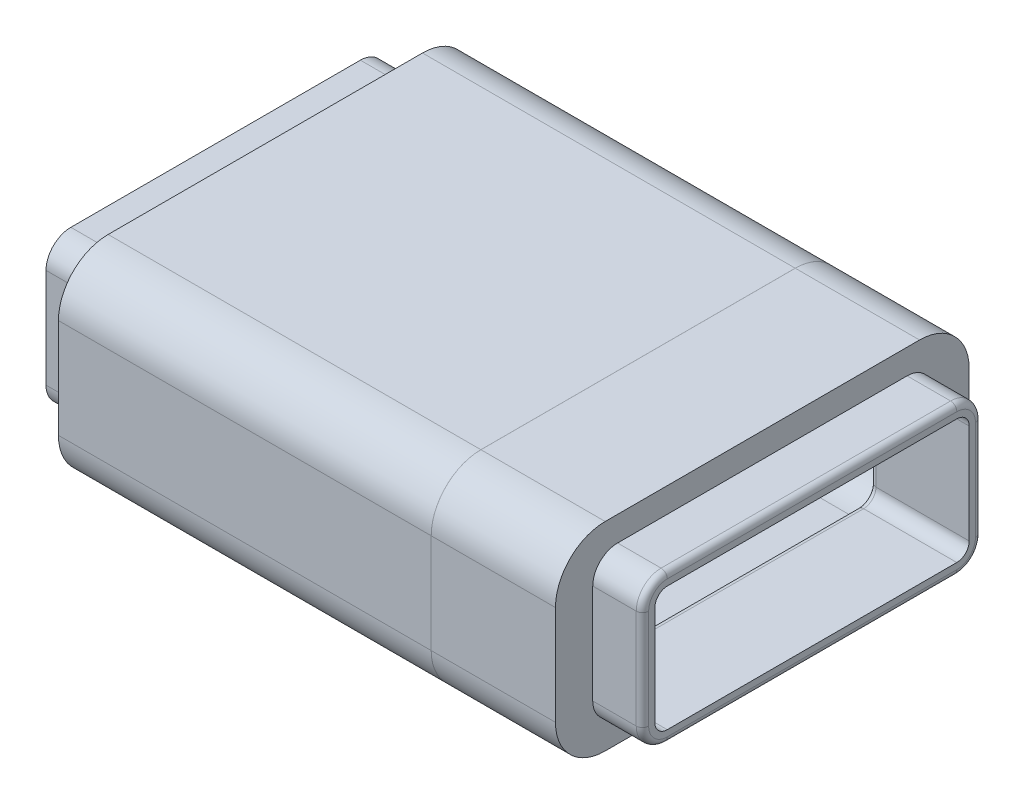
SolidWorks part; units mm, degrees
note: '?' marks a value the reader was unsure of.
ref_plane "Front" through (0, 0, 0) normal (0, 0, 1) x (1, 0, 0)
ref_plane "Top" through (0, 0, 0) normal (0, 1, 0) x (1, 0, 0)
ref_plane "Right" through (0, 0, 0) normal (1, 0, 0) x (0, 0, -1)
ref_plane "Plane4 polowki" through (0, 0, 0) normal (0, 0, 1) x (1, 0, 0)
sketch "Sketch2path" plane through (0, 0, 0) normal (0, 0, 1) x (1, 0, 0)
  line L0 (30.0026, 0) -> (40.0026, -0.0017)
  line L1 (0, 0) -> (30, 0)
  arc A1 (30, 0) -> (30.0026, 0) centre (30, -15) cw
  point P5 (30.0013, 0)
  dimension "D1" = 30
  dimension "D2" = 0.01
  dimension "D4" = 15
  dimension "D3" = 10
sketch "Sketch3" plane through (0, 0, 0) normal (1, 0, 0) x (0, 0, -1)
  line L0 (-16.65, -4) -> (-16.65, 4)
  line L1 (-12.65, 8) -> (12.65, 8)
  line L2 (16.65, 4) -> (16.65, -4)
  line L3 (12.65, -8) -> (-12.65, -8)
  line L4 (-15.65, -4) -> (-15.65, 4)
  line L5 (12.65, -7) -> (-12.65, -7)
  line L6 (0, 91.8161) -> (0, -91.8161) construction
  line L12 (15.65, 4) -> (15.65, -4)
  line L13 (-12.65, 7) -> (12.65, 7)
  arc A0 (-12.65, 8) -> (-16.65, 4) centre (-12.65, 4) ccw
  arc A1 (16.65, 4) -> (12.65, 8) centre (12.65, 4) ccw
  arc A2 (12.65, -8) -> (16.65, -4) centre (12.65, -4) ccw
  arc A3 (-16.65, -4) -> (-12.65, -8) centre (-12.65, -4) ccw
  arc A4 (-12.65, 7) -> (-15.65, 4) centre (-12.65, 4) ccw
  arc A5 (-15.65, -4) -> (-12.65, -7) centre (-12.65, -4) ccw
  arc A10 (12.65, -7) -> (15.65, -4) centre (12.65, -4) ccw
  arc A11 (15.65, 4) -> (12.65, 7) centre (12.65, 4) ccw
  dimension "D1" = 4
  dimension "D2" = 3
  dimension "D3" = 15.65
  dimension "D4" = 15.65
  dimension "D5" = 7
  dimension "D6" = 7
sweep "Sweep1" add profiles "Sketch3" path "Sketch2path"
ref_point "Point1S1"
ref_point "Point2S3"
ref_axis "os podluzna S1" through (0, 0, 0) along (-1, 0, 0)?
ref_axis "os podluzna S3" through (40.0026, -0.0017, 0) along (1, -0.0002, 0)?
sketch "Sketch4" plane through (40.0026, -0.007, 0) normal (1, -0.0002, 0) x (0, 0, -1)
  line L4 (0, 6.0052) -> (-11.65, 6.0052)
  line L5 (-13.65, 0) -> (-12.65, 0)
  line L6 (0, 5.0052) -> (0, 6.0052)
  line L8 (-12.65, -4.9948) -> (12.65, -4.9948)
  line L9 (13.65, -3.9948) -> (13.65, 4.0052)
  line L10 (12.65, 5.0052) -> (-12.65, 5.0052)
  line L11 (-13.65, 4.0052) -> (-13.65, -3.9948)
  line L14 (0, 5.0052) -> (-11.65, 5.0052)
  line L15 (-13.65, 4.0052) -> (-13.65, 0)
  line L16 (0, 0) -> (-20.2541, 0) construction
  line L17 (0, 0) -> (0, 12.5099) construction
  line L19 (-14.65, 4.0052) -> (-14.65, -3.9948) construction
  line L20 (-13.65, 4.0052) -> (-13.65, -3.9948) construction
  line L21 (-12.65, -4.9948) -> (12.65, -4.9948) construction
  line L22 (-12.65, -5.9948) -> (12.65, -5.9948) construction
  line L23 (14.65, -3.9948) -> (14.65, 4.0052) construction
  line L24 (13.65, -3.9948) -> (13.65, 4.0052) construction
  line L25 (12.65, 5.0052) -> (-12.65, 5.0052) construction
  line L26 (12.65, 6.0052) -> (-12.65, 6.0052) construction
  line L27 (-12.65, 4.0052) -> (-12.65, 0)
  line L28 (-13.65, 4.0052) -> (-13.65, 0)
  arc A5 (-11.65, 6.0052) -> (-13.65, 4.0052) centre (-11.65, 4.0052) ccw
  arc A6 (-11.65, 5.0052) -> (-12.65, 4.0052) centre (-11.65, 4.0052) ccw
  arc A8 (-13.65, -3.9948) -> (-12.65, -4.9948) centre (-12.65, -3.9948) ccw
  arc A9 (12.65, -4.9948) -> (13.65, -3.9948) centre (12.65, -3.9948) ccw
  arc A10 (13.65, 4.0052) -> (12.65, 5.0052) centre (12.65, 4.0052) ccw
  arc A11 (-12.65, 5.0052) -> (-13.65, 4.0052) centre (-12.65, 4.0052) ccw
  arc A16 (-14.65, -3.9948) -> (-12.65, -5.9948) centre (-12.65, -3.9948) ccw construction
  arc A17 (-13.65, -3.9948) -> (-12.65, -4.9948) centre (-12.65, -3.9948) ccw construction
  arc A18 (12.65, -4.9948) -> (13.65, -3.9948) centre (12.65, -3.9948) ccw construction
  arc A19 (12.65, -5.9948) -> (14.65, -3.9948) centre (12.65, -3.9948) ccw construction
  arc A20 (14.65, 4.0052) -> (12.65, 6.0052) centre (12.65, 4.0052) ccw construction
  arc A21 (13.65, 4.0052) -> (12.65, 5.0052) centre (12.65, 4.0052) ccw construction
  arc A22 (-12.65, 5.0052) -> (-13.65, 4.0052) centre (-12.65, 4.0052) ccw construction
  arc A23 (-12.65, 6.0052) -> (-14.65, 4.0052) centre (-12.65, 4.0052) ccw construction
  dimension "D1" = 3
  dimension "D2" = 1
extrude "Boss-Extrude1" add sketch "Sketch4" along normal mid plane 8 separate body contours A6 L14 L6 L4 A5 L15 L5 L27
mirror "Mirror1" about plane through (0, 0, 0) normal (0, 0, 1) of bodies 203
mirror "Mirror2" about plane through (44.0026, -0.0077, 0) normal (0.0002, 1, 0) of bodies 204
sketch "Sketch5" plane through (40.0026, -0.007, 0) normal (1, -0.0002, 0) x (0, 0, -1)
  line L0 (-15.65, 4.0052) -> (-15.65, -3.9948) construction
  line L1 (12.65, 7.0052) -> (-12.65, 7.0052) construction
  line L2 (15.65, -3.9948) -> (15.65, 4.0052) construction
  line L3 (-12.65, -6.9948) -> (12.65, -6.9948) construction
  line L4 (-15.65, 4.0052) -> (-15.65, -3.9948)
  line L5 (12.65, 7.0052) -> (-12.65, 7.0052)
  line L6 (15.65, -3.9948) -> (15.65, 4.0052)
  line L7 (-12.65, -6.9948) -> (12.65, -6.9948)
  line L8 (-13.65, 4.0052) -> (-13.65, -4.0052) construction
  line L9 (11.65, 6.0052) -> (-11.65, 6.0052) construction
  line L10 (13.65, 4.0052) -> (13.65, -4.0052) construction
  line L11 (11.65, -6.0052) -> (-11.65, -6.0052) construction
  line L12 (-13.65, 4.0052) -> (-13.65, -4.0052)
  line L13 (11.65, 6.0052) -> (-11.65, 6.0052)
  line L14 (13.65, 4.0052) -> (13.65, -4.0052)
  line L15 (11.65, -6.0052) -> (-11.65, -6.0052)
  arc A0 (-12.65, 7.0052) -> (-15.65, 4.0052) centre (-12.65, 4.0052) ccw construction
  arc A1 (15.65, 4.0052) -> (12.65, 7.0052) centre (12.65, 4.0052) ccw construction
  arc A2 (12.65, -6.9948) -> (15.65, -3.9948) centre (12.65, -3.9948) ccw construction
  arc A3 (-15.65, -3.9948) -> (-12.65, -6.9948) centre (-12.65, -3.9948) ccw construction
  arc A4 (-12.65, 7.0052) -> (-15.65, 4.0052) centre (-12.65, 4.0052) ccw
  arc A5 (15.65, 4.0052) -> (12.65, 7.0052) centre (12.65, 4.0052) ccw
  arc A6 (12.65, -6.9948) -> (15.65, -3.9948) centre (12.65, -3.9948) ccw
  arc A7 (-15.65, -3.9948) -> (-12.65, -6.9948) centre (-12.65, -3.9948) ccw
  arc A8 (-11.65, 6.0052) -> (-13.65, 4.0052) centre (-11.65, 4.0052) ccw construction
  arc A9 (13.65, 4.0052) -> (11.65, 6.0052) centre (11.65, 4.0052) ccw construction
  arc A10 (11.65, -6.0052) -> (13.65, -4.0052) centre (11.65, -4.0052) ccw construction
  arc A11 (-13.65, -4.0052) -> (-11.65, -6.0052) centre (-11.65, -4.0052) ccw construction
  arc A12 (-11.65, 6.0052) -> (-13.65, 4.0052) centre (-11.65, 4.0052) ccw
  arc A13 (13.65, 4.0052) -> (11.65, 6.0052) centre (11.65, 4.0052) ccw
  arc A14 (11.65, -6.0052) -> (13.65, -4.0052) centre (11.65, -4.0052) ccw
  arc A15 (-13.65, -4.0052) -> (-11.65, -6.0052) centre (-11.65, -4.0052) ccw
extrude "Boss-Extrude2" add sketch "Sketch5" against normal blind 4
fillet "Fillet1" radius 0.5 24 edges at (36.0037, 6.1203, 14.7713) (36.0038, 6.999, 0) (36.0037, 6.1203, -14.7713) (36.0026, -0.001, -15.65) (36.0015, -6.1224, -14.7713) (36.0014, -7.001, 0) (36.0015, -6.1224, 14.7713) (36.0026, -0.001, 15.65) (44.0026, -0.0077, 13.65) (44.0017, -5.4271, -13.0642) (44.0037, 5.9976, 0) (44.0036, 5.4118, 13.0642) (36.0026, -0.0063, 12.65) (36.0018, -4.7186, -12.3571) (36.0035, 4.999, 0) (36.0034, 4.7061, 12.3571) (36.0034, 4.7061, -12.3571) (44.0036, 5.4118, -13.0642) (44.0026, -0.0077, -13.65) (36.0026, -0.0063, -12.65) (36.0018, -4.7186, 12.3571) (36.0017, -5.0115, 0) (44.0016, -6.0129, 0) (44.0017, -5.4271, 13.0642)
sketch "Sketch6" plane through (0, 0, 0) normal (-1, 0, 0) x (0, 0, 1)
  line L0 (-12.65, 3.999) -> (-12.65, 0)
  line L1 (-13.65, 3.999) -> (-13.65, 0)
  line L2 (-13.65, 0) -> (-12.65, 0)
  line L3 (0, 4.999) -> (0, 5.999)
  line L5 (12.65, 5.999) -> (-12.65, 5.999) construction
  line L7 (0, 5.999) -> (-11.65, 5.999)
  line L8 (13.65, -4.001) -> (13.65, 3.999)
  line L9 (-12.65, -5.001) -> (12.65, -5.001)
  line L10 (-13.65, 3.999) -> (-13.65, -4.001)
  line L11 (12.65, 4.999) -> (-12.65, 4.999)
  line L14 (-13.65, 3.999) -> (-13.65, 0)
  line L15 (0, 4.999) -> (-11.65, 4.999)
  line L16 (0, 0) -> (-20.3439, 0) construction
  line L17 (-13.65, 3.999) -> (-13.65, -4.001) construction
  line L18 (0, -12.8536) -> (0, 12.8536) construction
  line L19 (0, 13.1279) -> (0, -6.001) construction
  line L20 (-12.65, -6.001) -> (12.65, -6.001) construction
  line L21 (-12.65, -5.001) -> (12.65, -5.001) construction
  line L22 (12.65, 4.999) -> (-12.65, 4.999) construction
  line L23 (-14.65, 3.999) -> (-14.65, -4.001) construction
  line L24 (13.65, -4.001) -> (13.65, 3.999) construction
  line L25 (14.65, -4.001) -> (14.65, 3.999) construction
  arc A0 (13.65, 3.999) -> (12.65, 4.999) centre (12.65, 3.999) ccw
  arc A1 (12.65, -5.001) -> (13.65, -4.001) centre (12.65, -4.001) ccw
  arc A2 (-13.65, -4.001) -> (-12.65, -5.001) centre (-12.65, -4.001) ccw
  arc A3 (-12.65, 4.999) -> (-13.65, 3.999) centre (-12.65, 3.999) ccw
  arc A4 (-11.65, 4.999) -> (-12.65, 3.999) centre (-11.65, 3.999) ccw
  arc A5 (-11.65, 5.999) -> (-13.65, 3.999) centre (-11.65, 3.999) ccw
  arc A12 (-13.65, -4.001) -> (-12.65, -5.001) centre (-12.65, -4.001) ccw construction
  arc A13 (-14.65, -4.001) -> (-12.65, -6.001) centre (-12.65, -4.001) ccw construction
  arc A14 (12.65, -6.001) -> (14.65, -4.001) centre (12.65, -4.001) ccw construction
  arc A15 (12.65, -5.001) -> (13.65, -4.001) centre (12.65, -4.001) ccw construction
  arc A16 (14.65, 3.999) -> (12.65, 5.999) centre (12.65, 3.999) ccw construction
  arc A17 (13.65, 3.999) -> (12.65, 4.999) centre (12.65, 3.999) ccw construction
  arc A18 (-12.65, 4.999) -> (-13.65, 3.999) centre (-12.65, 3.999) ccw construction
  arc A19 (-12.65, 5.999) -> (-14.65, 3.999) centre (-12.65, 3.999) ccw construction
  dimension "D1" = 2
  dimension "D2" = 1
extrude "Boss-Extrude3" add sketch "Sketch6" along normal mid plane 8 separate body contours L7 A5 L1 L2 L0 A4 L15 L3
mirror "Mirror3" about plane through (0, 0, 0) normal (0, 0, 1) of bodies 207
mirror "Mirror4" about plane through (-4, 0, 0) normal (0, 1, 0) of bodies 208
sketch "Sketch7" plane through (0, 0, 0) normal (-1, 0, 0) x (0, 0, 1)
  line L4 (-13.65, -3.999) -> (-13.65, 3.999)
  line L5 (-13.65, -3.999) -> (-13.65, 3.999)
  line L6 (11.65, -5.999) -> (-11.65, -5.999)
  line L7 (11.65, -5.999) -> (-11.65, -5.999)
  line L12 (13.65, 3.999) -> (13.65, -3.999)
  line L13 (13.65, 3.999) -> (13.65, -3.999)
  line L14 (-11.65, 5.999) -> (11.65, 5.999)
  line L15 (-11.65, 5.999) -> (11.65, 5.999)
  line L16 (-16.65, -4) -> (-16.65, 4)
  line L17 (-16.65, -4) -> (-16.65, 4)
  line L18 (-12.65, 8) -> (12.65, 8)
  line L19 (-12.65, 8) -> (12.65, 8)
  line L20 (16.65, 4) -> (16.65, -4)
  line L21 (16.65, 4) -> (16.65, -4)
  line L22 (12.65, -8) -> (-12.65, -8)
  line L23 (12.65, -8) -> (-12.65, -8)
  arc A4 (-13.65, -3.999) -> (-11.65, -5.999) centre (-11.65, -3.999) ccw
  arc A5 (-13.65, -3.999) -> (-11.65, -5.999) centre (-11.65, -3.999) ccw
  arc A6 (11.65, -5.999) -> (13.65, -3.999) centre (11.65, -3.999) ccw
  arc A7 (11.65, -5.999) -> (13.65, -3.999) centre (11.65, -3.999) ccw
  arc A8 (13.65, 3.999) -> (11.65, 5.999) centre (11.65, 3.999) ccw
  arc A9 (13.65, 3.999) -> (11.65, 5.999) centre (11.65, 3.999) ccw
  arc A10 (-11.65, 5.999) -> (-13.65, 3.999) centre (-11.65, 3.999) ccw
  arc A11 (-11.65, 5.999) -> (-13.65, 3.999) centre (-11.65, 3.999) ccw
  arc A12 (-12.65, 8) -> (-16.65, 4) centre (-12.65, 4) ccw
  arc A13 (-12.65, 8) -> (-16.65, 4) centre (-12.65, 4) ccw
  arc A14 (16.65, 4) -> (12.65, 8) centre (12.65, 4) ccw
  arc A15 (16.65, 4) -> (12.65, 8) centre (12.65, 4) ccw
  arc A16 (12.65, -8) -> (16.65, -4) centre (12.65, -4) ccw
  arc A17 (12.65, -8) -> (16.65, -4) centre (12.65, -4) ccw
  arc A18 (-16.65, -4) -> (-12.65, -8) centre (-12.65, -4) ccw
  arc A19 (-16.65, -4) -> (-12.65, -8) centre (-12.65, -4) ccw
extrude "Boss-Extrude5" add sketch "Sketch7" against normal blind 4
fillet "Fillet2" radius 0.5 24 edges at (4, 6.1213, 14.7713) (4, 0, 15.65) (4, -6.1213, 14.7713) (4, -7, 0) (4, -6.1213, -14.7713) (4, 0, -15.65) (4, 6.1213, -14.7713) (4, 7, 0) (-4, 0, -12.65) (-4, 4.7061, -12.3571) (-4, 4.999, 0) (-4, -4.7061, -12.3571) (-4, 4.7061, 12.3571) (-4, 0, 12.65) (-4, -4.999, 0) (4, 0, -12.65) (4, -4.7061, 12.3571) (4, 4.999, 0) (4, 4.7061, -12.3571) (4, 0, 12.65) (4, 4.7061, 12.3571) (4, -4.7061, -12.3571) (4, -4.999, 0) (-4, -4.7061, 12.3571)
ref_plane "Plane1 2 polowki na plasko" through (0, 0, 0) normal (0, -1, 0) x (-1, 0, 0)
other "SurfaceCut1prawa" [suppressed]
other "SurfaceCut3lewa" [suppressed]
